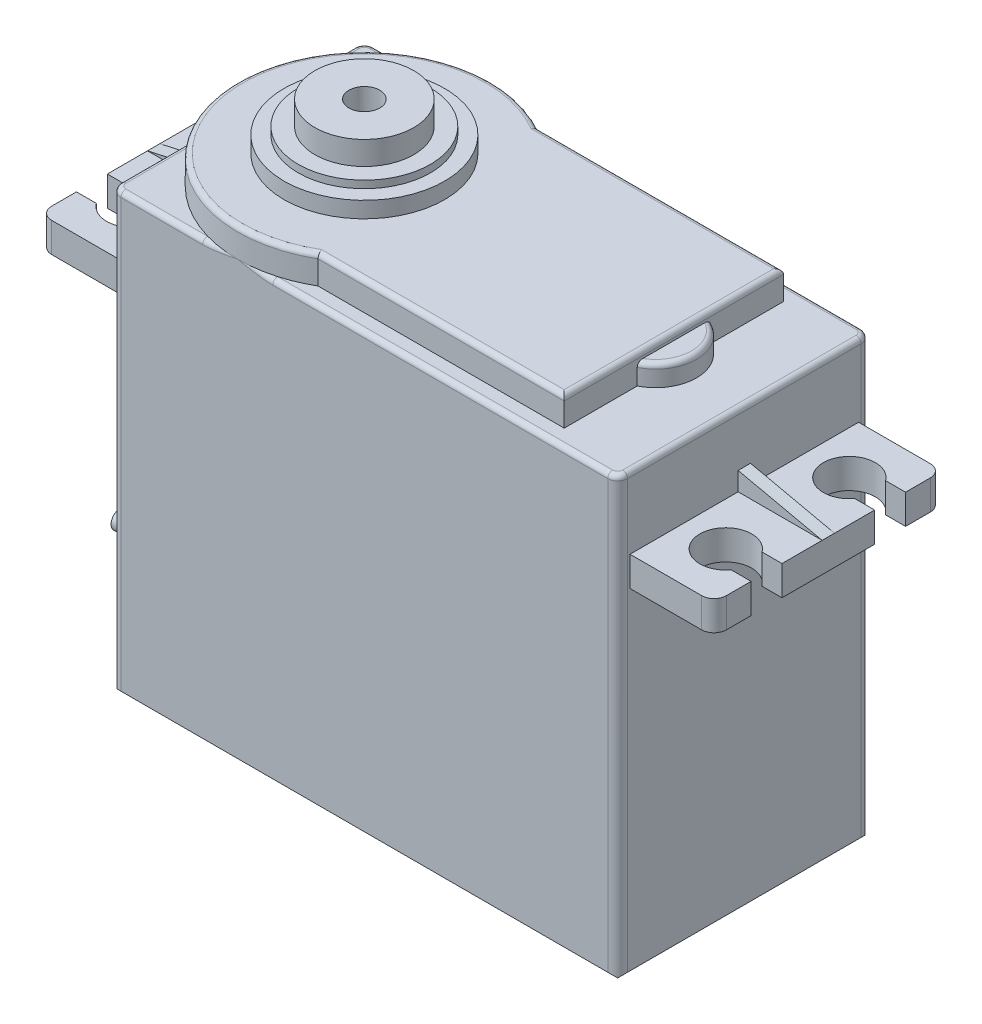
SolidWorks part; units mm, degrees
material "PE High Density"
ref_plane "Front Plane" through (0, 0, 0) normal (0, 0, 1) x (1, 0, 0)
ref_plane "Top Plane" through (0, 0, 0) normal (0, 1, 0) x (1, 0, 0)
ref_plane "Right Plane" through (0, 0, 0) normal (1, 0, 0) x (0, 0, -1)
sketch "Sketch1" plane through (0, 0, 0) normal (0, 1, 0) x (1, 0, 0)
  line L1 (-20.5, -10.25) -> (20.5, -10.25)
  line L2 (-20.5, -10.25) -> (-20.5, 10.25)
  line L3 (-20.5, 10.25) -> (20.5, 10.25)
  line L4 (20.5, -10.25) -> (20.5, 10.25)
  line L5 (-20.5, -10.25) -> (20.5, 10.25) construction
  line L6 (-20.5, 10.25) -> (20.5, -10.25) construction
  point P0 (0, 0)
  dimension "D1" = 41
  dimension "D2" = 20.5
extrude "Boss-Extrude1" add sketch "Sketch1" along normal blind 37
sketch "Sketch2" plane through (0, 37, 0) normal (0, 1, 0) x (1, 0, 0)
  line L0 (-20.5, 10.25) -> (-20.5, -10.25) construction
  line L1 (20.5, -10.25) -> (20.5, 10.25) construction
  line L2 (-5.122, -8.875) -> (14.8, -8.875)
  line L4 (-5.122, 8.875) -> (14.8, 8.875)
  line L5 (14.8, -8.875) -> (14.8, -2.9672)
  line L9 (14.8, 2.9672) -> (14.8, 8.875)
  arc A0 (-5.122, 8.875) -> (-5.122, -8.875) centre (-10.25, 0) ccw
  arc A1 (14.8, -2.9672) -> (14.8, 2.9672) centre (13.3208, 0) ccw
  point P5 (4.4919, 0)
  dimension "D1" = 10.25
  dimension "D2" = 17.75
  dimension "D3" = 5.7
extrude "Boss-Extrude2" add sketch "Sketch2" along normal blind 2.3
sketch "Sketch3" plane through (0, 39.3, 0) normal (0, 1, 0) x (1, 0, 0)
  circle A0 centre (-10.25, 0) radius 6.5
  dimension "D1" = 13
extrude "Boss-Extrude3" add sketch "Sketch3" along normal blind 1.3
sketch "Sketch4" plane through (0, 40.6, 0) normal (0, 1, 0) x (1, 0, 0)
  circle A0 centre (-10.25, 0) radius 5.35
  dimension "D1" = 10.7
extrude "Boss-Extrude4" add sketch "Sketch4" along normal blind 0.6
sketch "Sketch5" plane through (0, 39.3, 0) normal (0, 1, 0) x (1, 0, 0)
  line L0 (14.8, 2.9672) -> (14.8, -2.9672)
  arc A0 (14.8, -2.9672) -> (14.8, 2.9672) centre (13.3208, 0) ccw construction
  arc A1 (14.8, -2.9672) -> (14.8, 2.9672) centre (13.3208, 0) ccw
extrude "Cut-Extrude1" cut sketch "Sketch5" against normal blind 0.6
sketch "Sketch6" plane through (0, 41.2, 0) normal (0, 1, 0) x (1, 0, 0)
  circle A0 centre (-10.25, 0) radius 4
  dimension "D1" = 8
extrude "Boss-Extrude5" add sketch "Sketch6" along normal blind 1.9
chamfer "Chamfer1" distance 2 angle 45 4 edges at (-20.5, 0, 0) (0, 0, -10.25) (20.5, 0, 0) (0, 0, 10.25)
fillet "Fillet2" radius 0.8 4 edges at (-20.5, 19.5, -10.25) (-20.5, 19.5, 10.25) (20.5, 19.5, -10.25) (20.5, 19.5, 10.25)
sketch "Sketch7" plane through (-20.5, 0, 0) normal (-1, 0, 0) x (0, 0, 1)
  line L1 (-9.25, 31.2) -> (9.25, 31.2)
  line L2 (-9.25, 31.2) -> (-9.25, 28.8)
  line L3 (-9.25, 28.8) -> (9.25, 28.8)
  line L4 (9.25, 31.2) -> (9.25, 28.8)
  line L6 (-9.45, 37) -> (0, 37) construction
  line L9 (-10.25, 37) -> (-10.25, 2) construction
  dimension "D1" = 5.8
  dimension "D2" = 2.4
  dimension "D3" = 18.5
  dimension "D4" = 1
extrude "Boss-Extrude6" add sketch "Sketch7" along normal blind 6.8
sketch "Sketch9" plane through (0, 31.2, 0) normal (0, 1, 0) x (1, 0, 0)
  line L0 (-27.3, -9.25) -> (-27.3, 9.25) construction
  line L3 (-25.6875, 6.25) -> (-27.3, 6.25)
  line L4 (-21.6, 3.75) -> (-22.3125, 3.75)
  line L5 (-21.6, 3.75) -> (-21.6, 6.25)
  line L6 (-21.6, 6.25) -> (-22.3125, 6.25)
  line L7 (-27.3, 3.75) -> (-27.3, 6.25)
  line L8 (-21.6, 3.75) -> (-24, 5) construction
  line L9 (-21.6, 6.25) -> (-24, 5) construction
  line L10 (-21.6, -6.25) -> (-27.3, -6.25)
  line L11 (-21.6, -6.25) -> (-21.6, -3.75)
  line L12 (-21.6, -3.75) -> (-27.3, -3.75)
  line L13 (-27.3, -6.25) -> (-27.3, -3.75)
  line L14 (-21.6, -6.25) -> (-24, -5) construction
  line L15 (-21.6, -3.75) -> (-24, -5) construction
  line L18 (-25.6875, 3.75) -> (-27.3, 3.75)
  arc A0 (-25.6875, 3.75) -> (-25.6875, 6.25) centre (-24, 5) ccw
  arc A1 (-25.6875, -6.25) -> (-25.6875, -3.75) centre (-24, -5) ccw
  line M4 (-27.3, 9.25) -> (-27.3, -9.25)
  dimension "D1" = 4.2
  dimension "D2" = 4.2
  dimension "D3" = 3.3
  dimension "D4" = 10
  dimension "D5" = 5
  dimension "D6" = 2.5
  dimension "D7" = 2.5
  dimension "D8" = 3.3
extrude "Cut-Extrude2" cut sketch "Sketch9" against normal blind 6.8 contours A0 L3 L18 M4 | L12 A1 | L10 A1 | L10 A1 L12 M4 region at (-24.5093, 31.2, -5) region at (-24.6644, 31.2, 5) region at (-24, 31.2, 3.4033) region at (-24, 31.2, 6.5967)
fillet "Fillet1" radius 1 2 edges at (-27.3, 30, 9.25) (-27.3, 30, -9.25)
sketch "Sketch10" plane through (0, 31.2, 0) normal (0, 1, 0) x (1, 0, 0)
  line L0 (-20.5, -9.25) -> (-20.5, 9.25) construction
  line L1 (-27.3, -0.5) -> (-20.5, -0.5)
  line L2 (-27.3, -0.5) -> (-27.3, 0.5)
  line L3 (-27.3, 0.5) -> (-20.5, 0.5)
  line L4 (-20.5, -0.5) -> (-20.5, 0.5)
  line L5 (-27.3, -0.5) -> (-20.5, 0.5) construction
  line L6 (-27.3, 0.5) -> (-20.5, -0.5) construction
  line L7 (-27.3, -3.75) -> (-27.3, 3.75) construction
  point P0 (-23.9, 0)
  dimension "D1" = 1
extrude "Boss-Extrude7" add sketch "Sketch10" along normal blind 1.5
sketch "Sketch11" plane through (0, 0, 0.5) normal (0, 0, 1) x (1, 0, 0)
  line L0 (-27.3, 31.2) -> (-20.5, 32.7)
  line L1 (-20.5, 32.7) -> (-27.3, 32.7)
  line L2 (-27.3, 32.7) -> (-27.3, 31.2)
extrude "Cut-Extrude3" cut sketch "Sketch11" against normal blind 1.5
ref_plane "Plane1" through (0, 0, 0) normal (-1, 0, 0) x (0, 0, 1)
mirror "Mirror2" about plane through (0, 0, 0) normal (-1, 0, 0) of "Cut-Extrude3", "Boss-Extrude7", "Fillet1", "Cut-Extrude2", "Boss-Extrude6"
sketch "Sketch12" plane through (0, 43.1, 0) normal (0, 1, 0) x (1, 0, 0)
  circle A0 centre (-10.25, 0) radius 1.25
  dimension "D1" = 2.5
extrude "Cut-Extrude4" cut sketch "Sketch12" against normal blind 4
fillet "Fillet5" radius 0.4 5 edges at (16.6363, 38.7, 0) (14.8, 39.3, 0) (4.839, 39.3, -8.875) (-20.5, 39.3, 0) (4.839, 39.3, 8.875)
fillet "Fillet7" radius 0.4 11 edges at (20.2657, 37, 10.0157) (4.725, 37, 10.25) (-14.975, 37, 10.25) (-20.2657, 37, 10.0157) (-20.5, 37, 4.725) (-20.5, 37, -4.725) (-20.2657, 37, -10.0157) (-14.975, 37, -10.25) (4.725, 37, -10.25) (20.2657, 37, -10.0157) (20.5, 37, 0)
sketch "Sketch13" plane through (-20.5, 0, 0) normal (-1, 0, 0) x (0, 0, 1)
  line L0 (8.25, 0) -> (-8.25, 0) construction
  line L1 (-3.5, 3.2) -> (3.5, 3.2)
  line L2 (-3.5, 3.2) -> (-3.5, 7.4)
  line L3 (-3.5, 7.4) -> (3.5, 7.4)
  line L4 (3.5, 3.2) -> (3.5, 7.4)
  line L5 (-3.5, 3.2) -> (3.5, 7.4) construction
  line L6 (-3.5, 7.4) -> (3.5, 3.2) construction
  point P0 (0, 5.3)
  dimension "D1" = 7
  dimension "D2" = 4.2
  dimension "D3" = 3.2
extrude "Boss-Extrude8" add sketch "Sketch13" along normal blind 1
sketch "Sketch14" plane through (-21.5, 0, 0) normal (-1, 0, 0) x (0, 0, 1)
  line L9 (3.15, 3.55) -> (3.15, 7.05)
  line L10 (3.15, 7.05) -> (-3.15, 7.05)
  line L11 (-3.15, 7.05) -> (-3.15, 3.55)
  line L12 (-3.15, 3.55) -> (3.15, 3.55)
  line L13 (3.15, 3.55) -> (3.15, 7.05)
  line L14 (3.15, 7.05) -> (-3.15, 7.05)
  line L15 (-3.15, 7.05) -> (-3.15, 3.55)
  line L16 (-3.15, 3.55) -> (3.15, 3.55)
  dimension "D1" = 0.35
extrude "Boss-Extrude9" add sketch "Sketch14" along normal blind 4 draft 5 contours L14 L15 L16 L13
sketch "Sketch15" plane through (-25.5, 0, 0) normal (-1, 0, 0) x (0, 0, 1)
  line L0 (-2.8, 3.9) -> (2.8, 3.9) construction
  circle A0 centre (-1.5, 5.3) radius 0.75
  circle A1 centre (0, 5.3) radius 0.75
  circle A2 centre (1.5, 5.3) radius 0.75
  dimension "D1" = 1.5
  dimension "D2" = 1.5
  dimension "D3" = 1.5
  dimension "D4" = 1.4
extrude "Boss-Extrude12" add sketch "Sketch15" along normal blind 3 separate body contours A0 | A1 | A2 region at (-25.5, 5.3, -1.5) region at (-25.5, 5.3, 1.5) region at (-25.5, 5.3, 0)
sketch "Sketch16" plane through (0, 31.2, 0) normal (0, 1, 0) x (1, 0, 0)
  line L0 (-24, 5) -> (24, 5) construction
